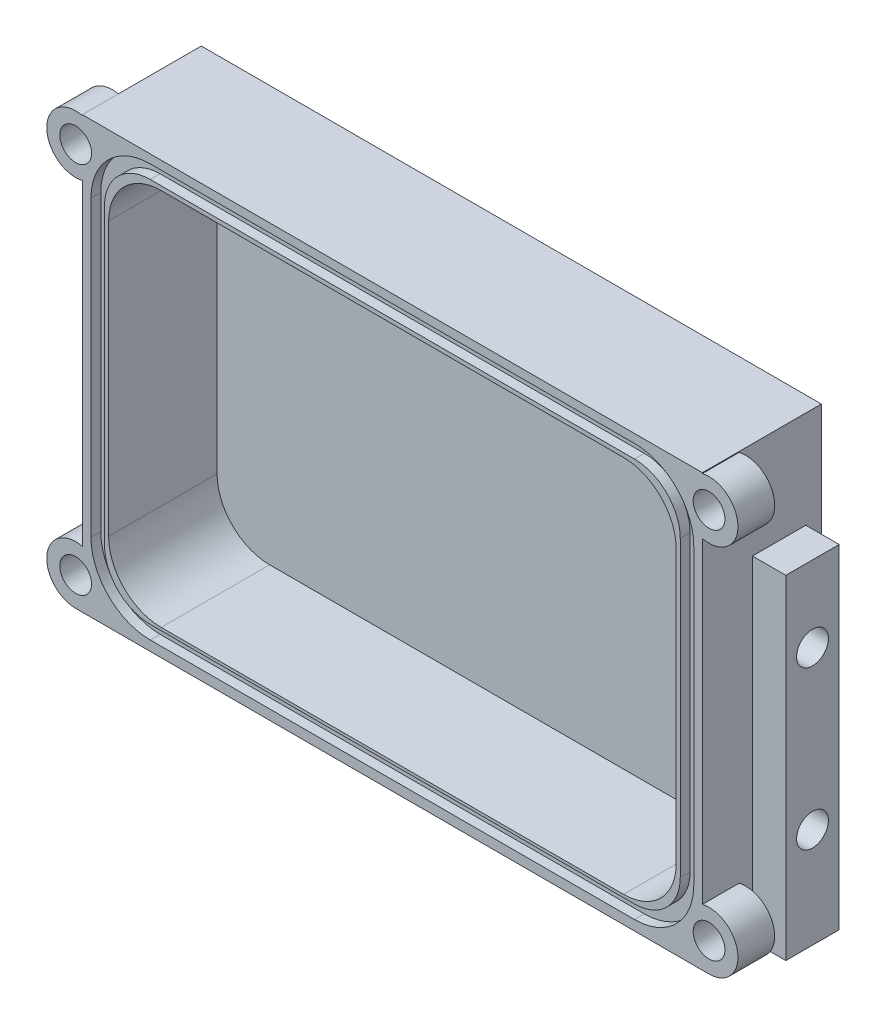
SolidWorks part; units mm, degrees
material "ABS PC"
ref_plane "X-Y Datum" through (0, 0, 0) normal (0, 0, 1) x (1, 0, 0)
ref_plane "X-Z Datum" through (0, 0, 0) normal (0, 1, 0) x (1, 0, 0)
ref_plane "Y-Z Datum" through (0, 0, 0) normal (1, 0, 0) x (0, 0, -1)
sketch "Sketch2" plane through (0, 0, 0) normal (0, 0, 1) x (1, 0, 0)
  line L1 (-54, 36) -> (54, 36)
  line L2 (-54, 36) -> (-54, -36)
  line L3 (-54, -36) -> (54, -36)
  line L4 (54, 36) -> (54, -36)
  line L5 (-54, 36) -> (54, -36) construction
  line L6 (-54, -36) -> (54, 36) construction
  point P0 (0, 0)
  dimension "D1" = 72
  dimension "D2" = 108
extrude "Boss-Extrude1" add sketch "Sketch2" along normal blind 20.64
shell "Shell1" thickness 5 removed face at (0, 0, 20.64) outward yes
sketch "Sketch3" plane through (0, 0, -5) normal (0, 0, -1) x (-1, 0, 0)
  line L4 (59, 41) -> (-59, 41)
  line L5 (-59, 41) -> (-59, -41)
  line L6 (-59, -41) -> (59, -41)
  line L7 (59, -41) -> (59, 41)
  line L8 (59, 41) -> (-59, 41)
  line L9 (-59, 41) -> (-59, -41)
  line L10 (-59, -41) -> (59, -41)
  line L11 (59, -41) -> (59, 41)
  dimension "D1" = 0
extrude "Cut-Extrude1" cut sketch "Sketch3" against normal blind 3
fillet "Fillet1" radius 10 4 edges at (54, -36, 10.32) (-54, -36, 10.32) (54, 36, 10.32) (-54, 36, 10.32)
sketch "Sketch13" plane through (0, 41, 0) normal (0, 1, 0) x (1, 0, 0)
  line L1 (-59, 2) -> (-75.51, 2)
  line L2 (-59, 2) -> (-59, -12.478)
  line L3 (-59, -12.478) -> (-75.51, -12.478)
  line L4 (-75.51, 2) -> (-75.51, -12.478)
  line L5 (-59, 2) -> (59, 2) construction
  line L6 (-75.51, -5.239) -> (-59, -5.239) construction
  line L7 (-59, -20.64) -> (-59, 2) construction
  circle A0 centre (-69.16, -5.239) radius 3.25
  dimension "D1" = 6.5
  dimension "D2" = 10.16
  dimension "D3" = 16.51
  dimension "D4" = 7.239
  dimension "D5" = 14.478
extrude "Boss-Extrude4" [suppressed] add sketch "Sketch13" against normal blind 3.175 contours A0 | L1 L4 L3 L2 | A0
mirror "Mirror4" [suppressed] about plane through (0, 0, 0) normal (1, 0, 0)
sketch "Sketch6" plane through (0, 0, 20.64) normal (0, 0, 1) x (1, 0, 0)
  line L0 (-59, -41) -> (59, -41) construction
  line L1 (60.27, -41) -> (59, -41)
  line L3 (12.452, 0) -> (-12.452, 0) construction
  line L6 (0, -12.452) -> (0, 12.452) construction
  line L7 (59, -41) -> (59, 41) construction
  line L8 (59, -41) -> (59, -40.8514)
  arc A2 (60.27, -41) -> (59, -40.8514) centre (60.27, -35.5) ccw
  circle A3 centre (60.27, -35.5) radius 3.025
  circle A6 centre (60.27, 35.5) radius 5.5
  circle A7 centre (60.27, 35.5) radius 3.025
  circle A8 centre (-60.27, -35.5) radius 3.025
  circle A9 centre (-60.27, -35.5) radius 5.5
  circle A10 centre (-60.27, 35.5) radius 3.025
  circle A11 centre (-60.27, 35.5) radius 5.5
  line M16 (59, -41) -> (59, 41)
  line M20 (-59, 41) -> (-59, -41)
  dimension "D1" = 11
  dimension "D2" = 6.05
  dimension "D3" = 1.27
extrude "Boss-Extrude2" add sketch "Sketch6" against normal blind 6.985 contours A11 A10 M20 | A8 M20 | A9 A8 M20 | A7 M16 | A7 A6 M16 | A3 A2 M16 | A3 A2 M16 | A8 M20 | A3 M16 | A3 M16 | A3 M16 | A3 M16 | A10 M20 | A8 region at (59.1292, 31.4516, 20.64) region at (59.635, -40.8708, 20.64) region at (58.277, -35.5, 20.64) region at (60.9021, -35.5, 20.64) region at (60.9021, 35.5, 20.64) region at (-58.277, -35.5, 20.64) region at (-60.9021, -35.5, 20.64) region at (-63.4242, -35.5, 20.64) region at (-65.6408, 35.5, 20.64) region at (-60.9021, 35.5, 20.64)
extrude "Cut-Extrude4" cut sketch "Sketch6<4>" against normal blind 6.35 contours A7 M16 | A7 M16 | A3 M16 | A3 M16 | A8 M20 | A8 M20 | A10 M20 | A10 M20 region at (58.277, -35.5, 20.64) region at (60.9021, -35.5, 20.64) region at (60.9021, 35.5, 20.64) region at (58.277, 35.5, 20.64) region at (-58.277, -35.5, 20.64) region at (-60.9021, -35.5, 20.64) region at (-58.277, 35.5, 20.64) region at (-60.9021, 35.5, 20.64)
sketch "Sketch6<4>" plane through (0, 0, 20.64) normal (0, 0, 1) x (1, 0, 0) same geometry as "Sketch6"
mirror "Mirror5" about plane through (0, 0, 0) normal (1, 0, 0) of "Cut-Extrude4", "Boss-Extrude2"
sketch "Sketch5" plane through (0, 0, 20.64) normal (0, 0, 1) x (1, 0, 0)
  line L0 (-46.0711, 38.0711) -> (46.0711, 38.0711) construction
  line L5 (56.0711, 28.0711) -> (56.0711, -27.825) construction
  line L6 (46.0711, -37.825) -> (-46.0711, -37.825) construction
  line L7 (-56.0711, -27.825) -> (-56.0711, 28.0711) construction
  line L8 (46.0711, -39.11) -> (-46.0711, -39.11)
  line L9 (-57.3561, -27.825) -> (-57.3561, 28.0711)
  line L10 (-46.0711, 39.3561) -> (46.0711, 39.3561)
  line L11 (57.3561, 28.0711) -> (57.3561, -27.825)
  line L12 (46.0711, -36.54) -> (-46.0711, -36.54)
  line L13 (-54.7861, -27.825) -> (-54.7861, 28.0711)
  line L14 (-46.0711, 36.7861) -> (46.0711, 36.7861)
  line L15 (54.7861, 28.0711) -> (54.7861, -27.825)
  line L16 (-44, -36) -> (44, -36) construction
  arc A0 (-49, 41) -> (-59, 31) centre (-49, 31) ccw construction
  arc A1 (59, 31) -> (49, 41) centre (49, 31) ccw construction
  arc A2 (56.0711, -27.825) -> (46.0711, -37.825) centre (46.0711, -27.825) cw construction
  arc A3 (46.0711, 38.0711) -> (56.0711, 28.0711) centre (46.0711, 28.0711) cw construction
  arc A4 (-46.0711, 38.0711) -> (-56.0711, 28.0711) centre (-46.0711, 28.0711) ccw construction
  arc A5 (-46.0711, -37.825) -> (-56.0711, -27.825) centre (-46.0711, -27.825) cw construction
  arc A6 (-46.0711, -39.11) -> (-57.3561, -27.825) centre (-46.0711, -27.825) cw
  arc A7 (-46.0711, 39.3561) -> (-57.3561, 28.0711) centre (-46.0711, 28.0711) ccw
  arc A8 (46.0711, 39.3561) -> (57.3561, 28.0711) centre (46.0711, 28.0711) cw
  arc A9 (57.3561, -27.825) -> (46.0711, -39.11) centre (46.0711, -27.825) cw
  arc A10 (-46.0711, -36.54) -> (-54.7861, -27.825) centre (-46.0711, -27.825) cw
  arc A11 (-46.0711, 36.7861) -> (-54.7861, 28.0711) centre (-46.0711, 28.0711) ccw
  arc A12 (46.0711, 36.7861) -> (54.7861, 28.0711) centre (46.0711, 28.0711) cw
  arc A13 (54.7861, -27.825) -> (46.0711, -36.54) centre (46.0711, -27.825) cw
  point P18 (56.0711, 38.0711)
  point P21 (-56.0711, 38.0711)
  dimension "D1" = 10
  dimension "D4" = 1.825
  dimension "D2" = 1.285
  dimension "D3" = 1.285
extrude "Cut-Extrude2" cut sketch "Sketch5" against normal blind 1.875
fillet "Fillet2" [suppressed] radius 15.08
fillet "Fillet3" [suppressed] radius 2.38
fillet "Fillet4" [suppressed] radius 4.92
fillet "Fillet5" [suppressed] radius 2.38
sketch "Sketch14" plane through (59, 0, 0) normal (1, 0, 0) x (0, 0, -1)
  line L0 (-13.655, -41) -> (-13.655, -30) construction
  line L1 (-11.115, -41) -> (-0.955, -41)
  line L2 (-11.115, -41) -> (-11.115, 22.5)
  line L3 (-11.115, 22.5) -> (-0.955, 22.5)
  line L4 (-0.955, -41) -> (-0.955, 22.5)
  line L5 (-13.655, -41) -> (2, -41) construction
  circle A0 centre (-6.035, 8.0499) radius 3.0251
  circle A1 centre (-6.035, -21.95) radius 3.0251
  dimension "D1" = 6.0503
  dimension "D2" = 5.08
  dimension "D3" = 10.16
  dimension "D4" = 63.5
  dimension "D5" = 19.05
  dimension "D6" = 29.9999
  dimension "D7" = 2.54
extrude "Boss-Extrude5" add sketch "Sketch14" along normal blind 6.35
mirror "Mirror6" about plane through (0, 0, 0) normal (1, 0, 0) of "Boss-Extrude5"
